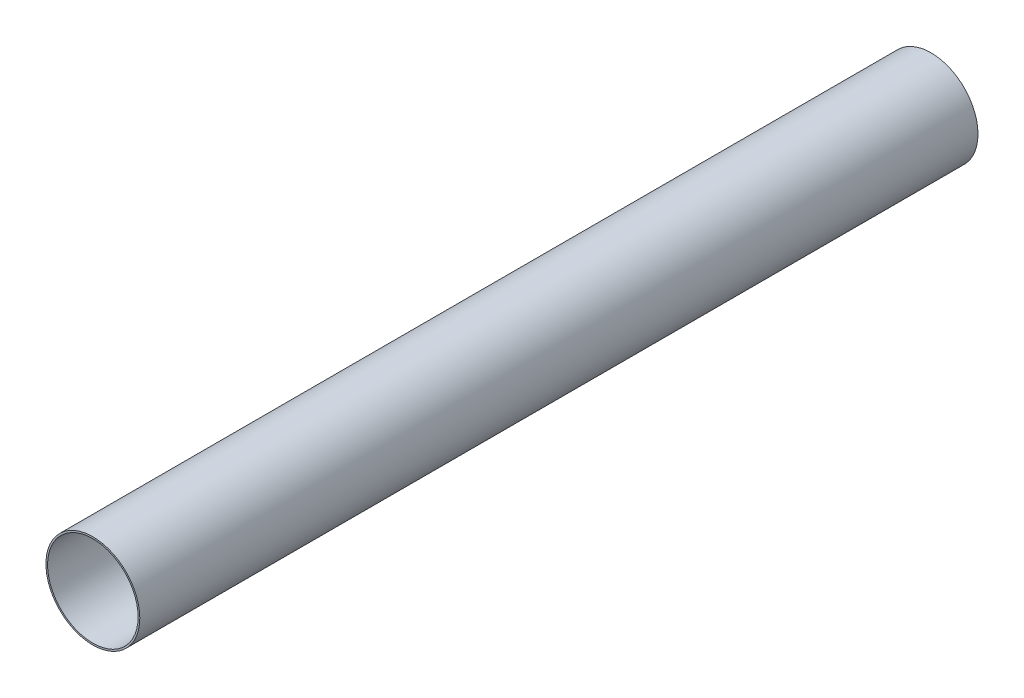
SolidWorks part; units mm, degrees
ref_plane "Front Plane" through (0, 0, 0) normal (0, 0, 1) x (1, 0, 0)
ref_plane "Top Plane" through (0, 0, 0) normal (0, 1, 0) x (1, 0, 0)
ref_plane "Right Plane" through (0, 0, 0) normal (1, 0, 0) x (0, 0, -1)
sketch "Sketch1" plane through (0, 0, 0) normal (0, 0, 1) x (1, 0, 0)
  circle A0 centre (0, 0) radius 14
  dimension "D1" = 28
extrude "Boss-Extrude1" add sketch "Sketch1" along normal blind 250
sketch "Sketch2" plane through (0, 0, 250) normal (0, 0, 1) x (1, 0, 0)
  circle A0 centre (0, 0) radius 13.5
  dimension "D1" = 27
extrude "Cut-Extrude1" cut sketch "Sketch2" against normal through all
